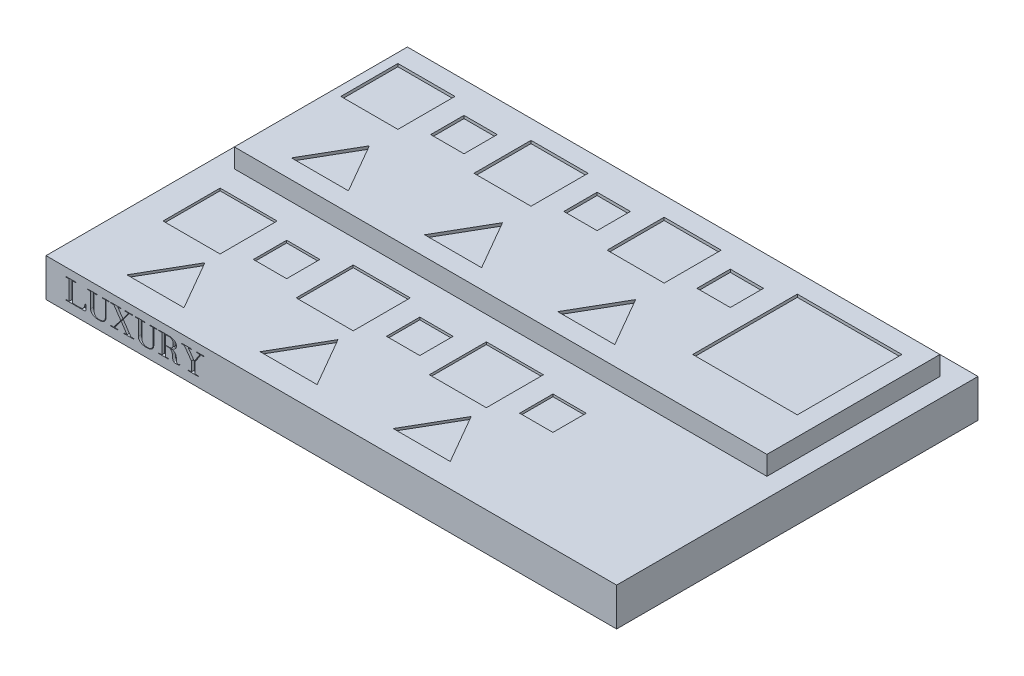
SolidWorks part; units mm, degrees
ref_plane "Front Plane" through (0, 0, 0) normal (0, 0, 1) x (1, 0, 0)
ref_plane "Top Plane" through (0, 0, 0) normal (0, 1, 0) x (1, 0, 0)
ref_plane "Right Plane" through (0, 0, 0) normal (1, 0, 0) x (0, 0, -1)
sketch "Sketch1" plane through (0, 0, 0) normal (0, 1, 0) x (1, 0, 0)
  line L21 (-300, 190) -> (300, 190)
  line L22 (-300, 190) -> (-300, -190)
  line L23 (-300, -190) -> (300, -190)
  line L24 (300, 190) -> (300, -190)
  line L25 (-300, 190) -> (300, -190) construction
  line L26 (-300, -190) -> (300, 190) construction
  point P0 (0, 0)
  dimension "D1" = 600
  dimension "D2" = 380
extrude "Boss-Extrude3" add sketch "Sketch1" against normal blind 40
sketch "Sketch2" plane through (0, 0, 190) normal (0, 0, 1) x (1, 0, 0)
  line L0 (-300, -40) -> (300, -40) construction
  line L1 (47.9838, -40) -> (47.9838, 0) construction
  line L2 (-280, -40) -> (-280, 0) construction
  line L3 (-300, 0) -> (300, 0) construction
  line L4 (-300, -40) -> (-300, 0) construction
  text T0 "LUXURY" font "BodoniFLF" height in points 70
  dimension "D1" = 10
  dimension "D2" = 20
extrude "Cut-Extrude1" cut sketch "Sketch2" against normal blind 3
sketch "Sketch3" plane through (0, 0, 0) normal (0, 1, 0) x (1, 0, 0)
  line L1 (-140, 170) -> (-280, 170)
  line L2 (-140, 170) -> (-140, -170)
  line L3 (-140, -170) -> (-280, -170)
  line L4 (-280, 170) -> (-280, -170)
  line L6 (300, 190) -> (-300, 190) construction
  line L7 (-300, 190) -> (-300, -190) construction
  line L15 (20, 170) -> (20, -170)
  line L16 (20, 170) -> (-120, 170)
  line L17 (-120, 170) -> (-120, -170)
  line L18 (20, -170) -> (-120, -170)
  line L19 (180, 170) -> (180, -170)
  line L20 (180, 170) -> (40, 170)
  line L21 (40, 170) -> (40, -170)
  line L22 (180, -170) -> (40, -170)
  line L23 (-300, -190) -> (300, -190) construction
  dimension "D1" = 140
  dimension "D2" = 3
  dimension "D3" = 20
  dimension "D4" = 20
  dimension "D6" = 20
  dimension "D5" = 20
sketch "Sketch5" plane through (0, 0, 0) normal (0, 1, 0) x (1, 0, 0)
  line L13 (-280, 170) -> (-280, -170) construction
  line L19 (-270, 150) -> (-210, 150)
  line L20 (-210, 60) -> (-240, 8.0385)
  line L21 (-240, 8.0385) -> (-180, 8.0385)
  line L22 (-180, 8.0385) -> (-210, 60)
  line L23 (-210, 150) -> (-210, 90)
  line L24 (-270, 90) -> (-210, 90)
  line L25 (-270, 150) -> (-270, 90)
  line L29 (-140, 170) -> (-140, -170) construction
  line L30 (-140, 170) -> (-280, 170) construction
  line L53 (300, -190) -> (300, 190) construction
  line L54 (300, 190) -> (-300, 190) construction
  circle A3 centre (-175, 130) radius 25
  point P37 (-160, 130)
  dimension "D22" = 35
  dimension "D14" = 30
  dimension "D17" = 60
  dimension "D19" = 10
  dimension "D20" = 20
extrude "Cut-Extrude2" cut sketch "Sketch5" against normal blind 3
sketch "Sketch6" plane through (0, 0, 0) normal (0, 1, 0) x (1, 0, 0)
  line L0 (-300, 190) -> (-300, -190) construction
  line L1 (-280, 170) -> (280, 170)
  line L2 (-280, 170) -> (-280, -11.9615)
  line L3 (-280, -11.9615) -> (280, -11.9615)
  line L4 (280, 170) -> (280, -11.9615)
  line L5 (300, -190) -> (300, 190) construction
  line L6 (300, 190) -> (-300, 190) construction
  line L7 (-240, 8.0385) -> (-180, 8.0385) construction
  dimension "D1" = 20
  dimension "D2" = 20
  dimension "D3" = 20
  dimension "D4" = 20
extrude "Boss-Extrude4" add sketch "Sketch6" along normal blind 20
sketch "Sketch8" plane through (0, 20, 0) normal (0, 1, 0) x (1, 0, 0)
  line L0 (-270, 90) -> (-270, 150)
  line L1 (-270, 150) -> (-210, 150)
  line L3 (-270, 90) -> (-210, 90)
  line L4 (-210, 150) -> (-210, 90)
  line L5 (-240, 8.0385) -> (-180, 8.0385)
  line L6 (-180, 8.0385) -> (-210, 60)
  line L7 (-210, 60) -> (-240, 8.0385)
  line L8 (-280, -11.9615) -> (280, -11.9615) construction
  line L9 (-280, 170) -> (-280, -11.9615) construction
  line L10 (280, 170) -> (-280, 170) construction
  line L11 (-130, 90) -> (-130, 150)
  line L12 (-130, 150) -> (-70, 150)
  line L13 (-70, 150) -> (-70, 90)
  line L14 (-130, 90) -> (-70, 90)
  line L15 (-100, 8.0385) -> (-40, 8.0385)
  line L16 (-40, 8.0385) -> (-70, 60)
  line L17 (-70, 60) -> (-100, 8.0385)
  line L18 (10, 90) -> (10, 150)
  line L19 (10, 150) -> (70, 150)
  line L20 (70, 150) -> (70, 90)
  line L21 (10, 90) -> (70, 90)
  line L22 (40, 8.0385) -> (100, 8.0385)
  line L23 (100, 8.0385) -> (70, 60)
  line L24 (70, 60) -> (40, 8.0385)
  line L26 (150, 150) -> (260, 150)
  line L27 (150, 150) -> (150, 40)
  line L28 (150, 40) -> (260, 40)
  line L29 (260, 150) -> (260, 40)
  line L30 (280, -11.9615) -> (280, 170) construction
  line L31 (-48, 137.5) -> (-48, 102.5)
  line L32 (-270, -36.9615) -> (-210, -36.9615)
  line L33 (-270, -36.9615) -> (-270, -96.9615)
  line L34 (-270, -96.9615) -> (-210, -96.9615)
  line L35 (-210, -36.9615) -> (-210, -96.9615)
  line L39 (-130, -36.9615) -> (-130, -96.9615)
  line L40 (-130, -36.9615) -> (-70, -36.9615)
  line L41 (-70, -36.9615) -> (-70, -96.9615)
  line L42 (-130, -96.9615) -> (-70, -96.9615)
  line L46 (10, -36.9615) -> (10, -96.9615)
  line L47 (10, -36.9615) -> (70, -36.9615)
  line L48 (70, -36.9615) -> (70, -96.9615)
  line L49 (10, -96.9615) -> (70, -96.9615)
  line L53 (-280, 170) -> (-280, -11.9615) construction
  line L54 (-188, 137.5) -> (-153, 137.5)
  line L55 (-188, 137.5) -> (-188, 102.5)
  line L56 (-188, 102.5) -> (-153, 102.5)
  line L57 (-153, 137.5) -> (-153, 102.5)
  line L58 (-48, 137.5) -> (-13, 137.5)
  line L59 (-13, 137.5) -> (-13, 102.5)
  line L60 (-48, 102.5) -> (-13, 102.5)
  line L61 (92, 137.5) -> (92, 102.5)
  line L62 (92, 137.5) -> (127, 137.5)
  line L63 (127, 137.5) -> (127, 102.5)
  line L64 (92, 102.5) -> (127, 102.5)
  line L66 (-240, -164.923) -> (-180, -164.923)
  line L67 (-180, -164.923) -> (-210, -112.9615)
  line L68 (-210, -112.9615) -> (-240, -164.923)
  line L69 (-100, -164.923) -> (-40, -164.923)
  line L70 (-40, -164.923) -> (-70, -112.9615)
  line L71 (-70, -112.9615) -> (-100, -164.923)
  line L72 (40, -164.923) -> (100, -164.923)
  line L73 (100, -164.923) -> (70, -112.9615)
  line L74 (70, -112.9615) -> (40, -164.923)
  line L75 (-47.5, -49.4615) -> (-47.5, -84.4615)
  line L76 (-187.5, -49.4615) -> (-152.5, -49.4615)
  line L77 (-187.5, -49.4615) -> (-187.5, -84.4615)
  line L78 (-187.5, -84.4615) -> (-152.5, -84.4615)
  line L79 (-152.5, -49.4615) -> (-152.5, -84.4615)
  line L80 (-47.5, -49.4615) -> (-12.5, -49.4615)
  line L81 (-12.5, -49.4615) -> (-12.5, -84.4615)
  line L82 (-47.5, -84.4615) -> (-12.5, -84.4615)
  line L83 (92.5, -49.4615) -> (92.5, -84.4615)
  line L84 (92.5, -49.4615) -> (127.5, -49.4615)
  line L85 (127.5, -49.4615) -> (127.5, -84.4615)
  line L86 (92.5, -84.4615) -> (127.5, -84.4615)
  circle A1 centre (-210, 25.359) radius 17.3205 construction
  circle A10 centre (-210, -147.6025) radius 17.3205 construction
  point P20 (-210, 120)
  point P33 (-188, 120)
  point P47 (-70, 120)
  point P66 (0, 0)
  point P81 (-187.5, -66.9615)
  point P82 (-210, -66.9615)
  dimension "D2" = 35
  dimension "D3" = 20
  dimension "D6" = 22
  dimension "D19" = 16
  dimension "D1" = 60
  dimension "D4" = 10
  dimension "D5" = 20
  dimension "D8" = 80
  dimension "D9" = 110
  dimension "D10" = 20
  dimension "D11" = 20
  dimension "D12" = 3
  dimension "D13" = 22
  dimension "D14" = 3
  dimension "D15" = 10
  dimension "D16" = 25
  dimension "D17" = 80
  dimension "D18" = 60
  dimension "D20" = 80
  dimension "D24" = 35
  dimension "D25" = 22.5
  dimension "D27" = 22.5
  dimension "D7" = 3
  dimension "D22" = 3
  dimension "D26" = 3
extrude "Cut-Extrude12" cut sketch "Sketch8" against normal blind 3 contours L4 L1 L0 L3 | L57 L54 L55 L56 | L23 L24 L22 | L29 L26 L27 L28 | L61 L64 L63 L62 | L18 L21 L20 L19 | L31 L60 L59 L58 | L7 L5 L6 | L17 L15 L16 | L11 L12 L13 L14 region at (-240, 20, -120) region at (40, 20, -120) region at (70, 20, -25.359) region at (205, 20, -95) region at (-30.5, 20, -120) region at (-170.5, 20, -120) region at (109.5, 20, -120)
extrude "Cut-Extrude13" cut sketch "Sketch8<7>" against normal offset from surface (22.5 mm away) 37.5 contours L35 L32 L33 L34 | L79 L76 L77 L78 | L39 L42 L41 L40 | L75 L82 L81 L80 | L46 L49 L48 L47 | L83 L86 L85 L84 | L73 L74 L72 | L70 L71 L69 | L67 L68 L66 region at (-240, 20, 66.9615) region at (-100, 20, 66.9615) region at (40, 20, 66.9615) region at (-210, 20, 147.6025) region at (-70, 20, 147.6025) region at (70, 20, 147.6025) region at (-30, 20, 66.9615) region at (-170, 20, 66.9615) region at (110, 20, 66.9615) up to face at (0, -40, 0)
sketch "Sketch8<7>" plane through (0, 20, 0) normal (0, 1, 0) x (1, 0, 0) same geometry as "Sketch8"
